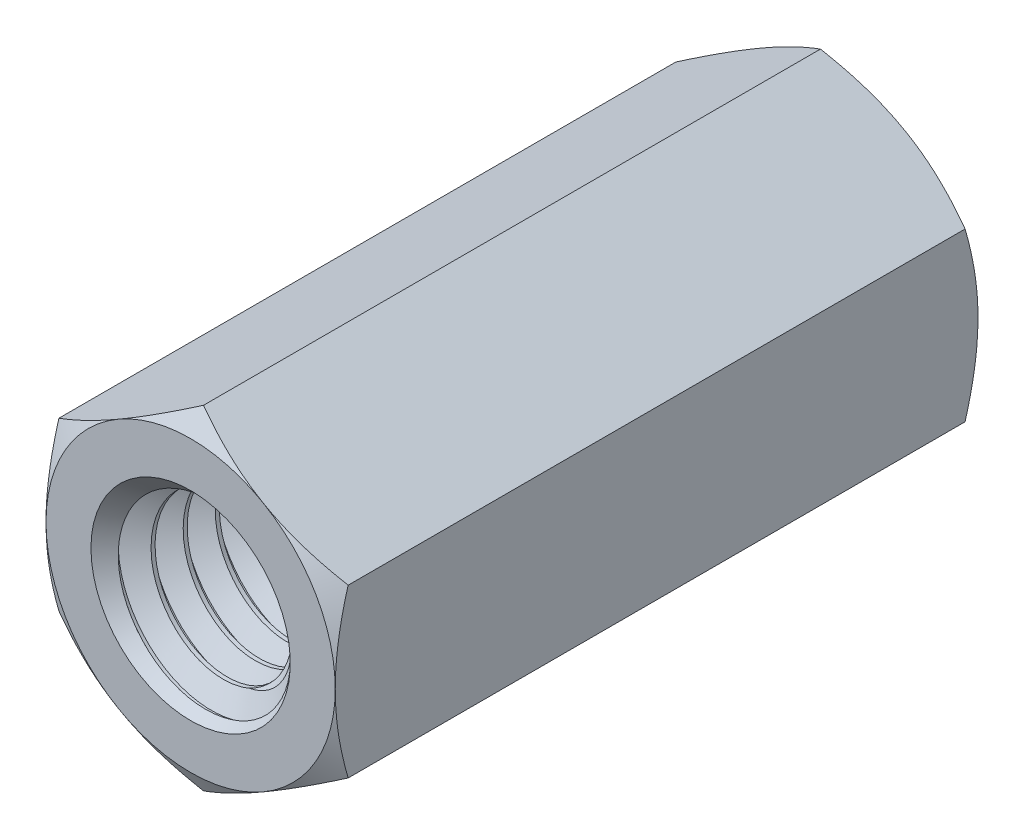
SolidWorks part; units mm, degrees
ref_plane "Front Plane" through (0, 0, 0) normal (0, 0, 1) x (1, 0, 0)
ref_plane "Top Plane" through (0, 0, 0) normal (0, 1, 0) x (1, 0, 0)
ref_plane "Right Plane" through (0, 0, 0) normal (1, 0, 0) x (0, 0, -1)
sketch "Sketch3" plane through (0, 0, 0) normal (1, 0, 0) x (0, 0, -1)
  line L0 (-5, 0) -> (5, 0) construction
  line L1 (0, 2.25) -> (0, -2.25) construction
  line L2 (-5, 1.5) -> (-5, -1.5) construction
  point P2 (0.2, 0)
  point P3 (-0.2, 0)
  dimension "Length" = 10
  dimension "Min Thread Length" = 4.8
  dimension "D1" = 4.8
  dimension "Thread Dia" = 3
  dimension "Hex" = 4.5
sketch "Sketch1" plane through (0, 0, 0) normal (0, 0, 1) x (1, 0, 0)
  line L1 (0, 2.5981) -> (-2.25, 1.299)
  line L2 (-2.25, 1.299) -> (-2.25, -1.299)
  line L3 (-2.25, -1.299) -> (0, -2.5981)
  line L4 (0, -2.5981) -> (2.25, -1.299)
  line L5 (2.25, -1.299) -> (2.25, 1.299)
  line L6 (2.25, 1.299) -> (0, 2.5981)
  circle A0 centre (0, 0) radius 2.25 construction
  circle A1 centre (0, 0) radius 1.5
extrude "Extrude1" add sketch "Sketch1" along normal up to vertex (5 mm away) and the other way up to vertex (5 mm away) up to point (0, 0, 5) other way up to point (0, 0, -5)
sketch "Sketch11" plane through (0, 0, -5) normal (0, 0, -1) x (-1, 0, 0)
  circle A0 centre (0, 0) radius 1.5 construction
  circle A1 centre (0, 0) radius 1.5
curve "Helix/Spiral1" pitch 0.5 height 10.5 radius 1.5 centre (0, 0, -5) axis (0, 0, 1) start towards (0, 1, 0) parameters "Pitch"=0.5
sketch "Sketch12" plane through (0, 0, 0) normal (1, 0, 0) x (0, 0, -1)
  line L0 (5.4375, 1.5) -> (5, 1.5)
  line L1 (5.4375, 1.5) -> (5.25, 1.1752)
  line L2 (5.25, 1.1752) -> (5.1875, 1.1752)
  line L3 (5.1875, 1.1752) -> (5, 1.5)
  line L4 (5.2188, 1.1752) -> (5.2188, 1.5) construction
  line L5 (5.3438, 1.3376) -> (5.0938, 1.3376) construction
  dimension "D1" = 0.0625
  dimension "D2" = 0.25
  dimension "D3" = 60
sweep "Sweep1" add profiles "Sketch12" path "Helix/Spiral1"
sketch "Sketch6" plane through (0, 0, -5) normal (0, 0, -1) x (-1, 0, 0)
  line L6 (0, 2.5981) -> (-2.25, 1.299)
  line L7 (-2.25, 1.299) -> (-2.25, -1.299)
  line L8 (-2.25, -1.299) -> (0, -2.5981)
  line L9 (0, -2.5981) -> (2.25, -1.299)
  line L10 (2.25, -1.299) -> (2.25, 1.299)
  line L11 (2.25, 1.299) -> (0, 2.5981)
  line L12 (0, 2.5981) -> (-2.25, 1.299)
  line L13 (-2.25, 1.299) -> (-2.25, -1.299)
  line L14 (-2.25, -1.299) -> (0, -2.5981)
  line L15 (0, -2.5981) -> (2.25, -1.299)
  line L16 (2.25, -1.299) -> (2.25, 1.299)
  line L17 (2.25, 1.299) -> (0, 2.5981)
  dimension "D1" = 0
extrude "Extrude2" cut sketch "Sketch6" along normal through all
sketch "Sketch7" plane through (0, 0, -5) normal (0, 0, -1) x (-1, 0, 0)
  circle A2 centre (0, 0) radius 1.5508
  circle A3 centre (0, 0) radius 1.5508
  dimension "D1" = 0.0508
extrude "Extrude3" cut sketch "Sketch7" against normal through all draft 43
sketch "Sketch8" plane through (0, 0, -5) normal (0, 0, -1) x (-1, 0, 0)
  circle A0 centre (0, 0) radius 2.25 construction
  circle A1 centre (0, 0) radius 2.25
extrude "Extrude4" cut sketch "Sketch8" against normal through all draft 60 flip side to cut
mirror "Mirror1" about plane through (0, 0, 0) normal (0, 0, 1) of "Extrude2", "Extrude3", "Extrude4"
sketch "Sketch9" [suppressed] plane through (0, 0, 0) normal (1, 0, 0) x (0, 0, -1)
  line L1 (-1.2, 1.1353) -> (1.2, 1.1353)
  line L2 (-1.2, 1.1353) -> (-1.2, 0)
  line L3 (-1.2, 0) -> (1.2, 0)
  line L4 (1.2, 1.1353) -> (1.2, 0)
  line L7 (-6, 0) -> (6, 0) construction
revolve "Revolve" [suppressed] add sketch "Sketch9" angle 360 about L0
sketch "Sketch10" [suppressed] plane through (0, 0, 0) normal (1, 0, 0) x (0, 0, -1)
  line L0 (6, 1.25) -> (1.2, 1.25)
  line L1 (-6, 1.25) -> (-1.2, 1.25)
  line L2 (1.2, 1.25) -> (1.2, -1.25)
  line L3 (-6, -1.25) -> (-1.2, -1.25)
  line L4 (-1.2, 1.25) -> (-1.2, -1.25)
  line L5 (1.2, -1.25) -> (6, -1.25)
equation "\"D1@Sketch3\" = \"Min Thread Length@Sketch3\""
equation "\"D3@Helix/Spiral1\" = \"Length@Sketch3\"+\"Pitch@Helix/Spiral1\""
equation "\"D1@Sketch12\" = \"Pitch@Helix/Spiral1\"*.125"
equation "\"D2@Sketch12\" = \"Pitch@Helix/Spiral1\"*.5"
